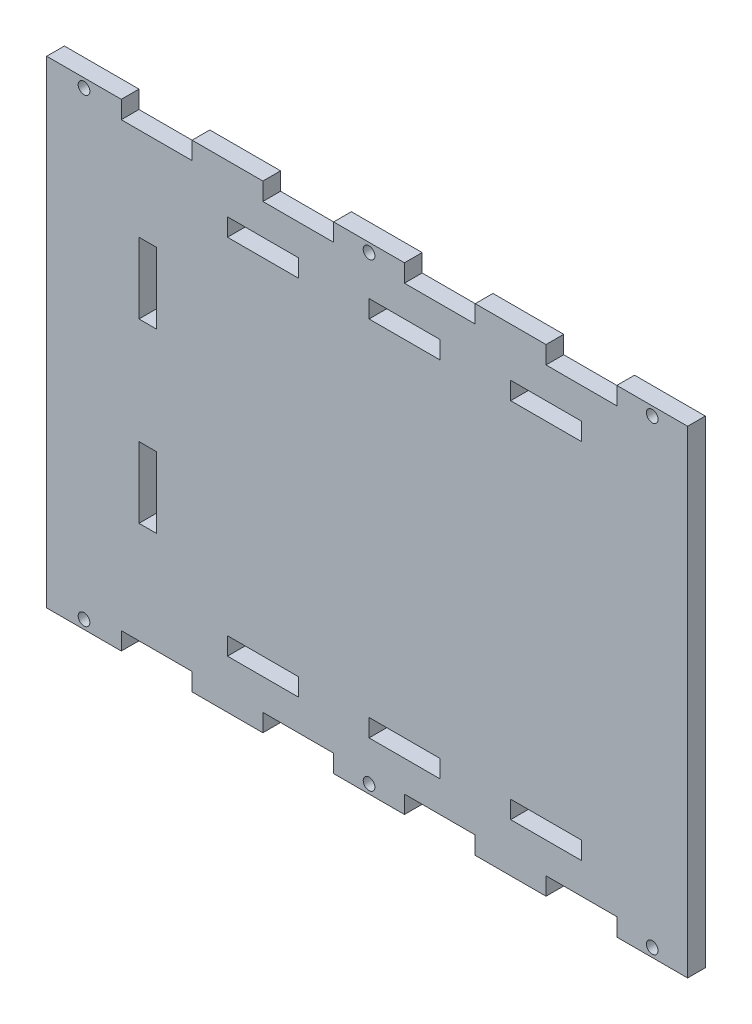
SolidWorks part; units mm, degrees
ref_plane "Front Plane" through (0, 0, 0) normal (0, 0, 1) x (1, 0, 0)
ref_plane "Top Plane" through (0, 0, 0) normal (0, 1, 0) x (1, 0, 0)
ref_plane "Right Plane" through (0, 0, 0) normal (1, 0, 0) x (0, 0, -1)
sketch "Sketch1" plane through (0, 0, 0) normal (0, 0, 1) x (1, 0, 0)
  line L1 (90.6195, 155.575) -> (-139.3499, 155.575)
  line L2 (90.6195, 155.575) -> (90.6195, -15.875)
  line L3 (90.6195, -15.875) -> (-139.3499, -15.875)
  line L4 (-139.3499, 155.575) -> (-139.3499, -15.875)
extrude "Boss-Extrude1" add sketch "Sketch1" along normal blind 6.35
sketch "Sketch2" plane through (0, 0, 6.35) normal (0, 0, 1) x (1, 0, 0)
  line L0 (-139.3499, -15.875) -> (90.6195, -15.875) construction
  line L1 (-112.5805, -9.525) -> (-87.1805, -9.525)
  line L2 (-112.5805, -9.525) -> (-112.5805, -15.875)
  line L3 (-112.5805, -15.875) -> (-87.1805, -15.875)
  line L4 (-87.1805, -9.525) -> (-87.1805, -15.875)
  line L5 (-87.1805, -9.525) -> (-87.1805, -15.875) construction
  line L6 (90.6195, 155.575) -> (-139.3499, 155.575) construction
  line L7 (-112.5805, 149.225) -> (-87.1805, 149.225)
  line L8 (-112.5805, 149.225) -> (-112.5805, 155.575)
  line L9 (-112.5805, 155.575) -> (-87.1805, 155.575)
  line L10 (-87.1805, 149.225) -> (-87.1805, 155.575)
  line L11 (-87.1805, 149.225) -> (-87.1805, 155.575) construction
extrude "Cut-Extrude1" cut sketch "Sketch2" against normal blind 6.35
pattern_linear "LPattern1" count 4 spacing 50.8 along (1, 0, 0) of "Cut-Extrude1"
sketch "Sketch4" plane through (0, 0, 0) normal (0, 0, -1) x (-1, 0, 0)
  line L0 (128.0988, -9.525) -> (123.8316, -15.875) construction
  line L1 (139.3499, -15.875) -> (112.5805, -15.875) construction
  line L2 (123.8316, -9.525) -> (123.8316, -15.875) construction
  line L3 (123.8316, -9.525) -> (128.0988, -15.875) construction
  line L4 (128.0988, -9.525) -> (128.0988, -15.875) construction
  line L5 (21.5469, -9.525) -> (25.8141, -15.875) construction
  line L6 (36.3805, -15.875) -> (10.9805, -15.875) construction
  line L7 (25.8141, -9.525) -> (25.8141, -15.875) construction
  line L8 (25.8141, -9.525) -> (21.5469, -15.875) construction
  line L9 (-75.7859, -9.525) -> (-80.0531, -15.875) construction
  line L10 (-65.2195, -15.875) -> (-90.6195, -15.875) construction
  line L11 (-80.0531, -9.525) -> (-80.0531, -15.875) construction
  line L12 (-80.0531, -9.525) -> (-75.7859, -15.875) construction
  line L13 (123.8316, 149.225) -> (128.0988, 155.575) construction
  line L14 (112.5805, 155.575) -> (139.3499, 155.575) construction
  line L15 (128.0988, 149.225) -> (128.0988, 155.575) construction
  line L16 (128.0988, 149.225) -> (123.8316, 155.575) construction
  line L17 (21.5469, 149.225) -> (25.8141, 155.575) construction
  line L18 (10.9805, 155.575) -> (36.3805, 155.575) construction
  line L19 (25.8141, 149.225) -> (25.8141, 155.575) construction
  line L20 (25.8141, 149.225) -> (21.5469, 155.575) construction
  line L21 (-75.7859, 149.225) -> (-80.0531, 155.575) construction
  line L22 (-90.6195, 155.575) -> (-65.2195, 155.575) construction
  line L23 (-80.0531, 149.225) -> (-75.7859, 155.575) construction
  line L24 (-75.7859, 149.225) -> (-75.7859, 155.575) construction
  circle A0 centre (-77.9195, -12.7) radius 2.0955
  circle A1 centre (23.6805, -12.7) radius 2.0955
  circle A2 centre (125.9652, -12.7) radius 2.0955
  circle A3 centre (125.9652, 152.4) radius 2.0955
  circle A4 centre (23.6805, 152.4) radius 2.0955
  circle A5 centre (-77.9195, 152.4) radius 2.0955
  dimension "D1" = 4.191
extrude "Cut-Extrude2" cut sketch "Sketch4" against normal through all
sketch "Sketch5" plane through (0, 0, 0) normal (0, 0, -1) x (-1, 0, 0)
  line L0 (-1.7195, 7.9375) -> (23.6805, 7.9375) construction
  line L1 (-52.5195, 1.5875) -> (-27.1195, 1.5875)
  line L2 (-52.5195, 1.5875) -> (-52.5195, 7.9375)
  line L3 (-52.5195, 7.9375) -> (-27.1195, 7.9375)
  line L4 (-27.1195, 1.5875) -> (-27.1195, 7.9375)
  line L5 (-1.7195, 1.5875) -> (23.6805, 1.5875)
  line L6 (-1.7195, 1.5875) -> (-1.7195, 7.9375)
  line L7 (-1.7195, 7.9375) -> (23.6805, 7.9375)
  line L8 (23.6805, 1.5875) -> (23.6805, 7.9375)
  line L9 (106.2305, 90.4875) -> (106.2305, 115.8875) construction
  line L10 (49.0805, 1.5875) -> (74.4805, 1.5875)
  line L11 (49.0805, 1.5875) -> (49.0805, 7.9375)
  line L12 (49.0805, 7.9375) -> (74.4805, 7.9375)
  line L13 (74.4805, 1.5875) -> (74.4805, 7.9375)
  line L14 (99.8805, 26.9875) -> (106.2305, 26.9875)
  line L15 (99.8805, 26.9875) -> (99.8805, 52.3875)
  line L16 (99.8805, 52.3875) -> (106.2305, 52.3875)
  line L17 (106.2305, 26.9875) -> (106.2305, 52.3875)
  line L18 (99.8805, 90.4875) -> (106.2305, 90.4875)
  line L19 (99.8805, 90.4875) -> (99.8805, 115.8875)
  line L20 (99.8805, 115.8875) -> (106.2305, 115.8875)
  line L21 (106.2305, 90.4875) -> (106.2305, 115.8875)
  line L22 (106.2305, 115.8875) -> (99.8805, 115.8875) construction
  line L24 (49.0805, 131.7625) -> (74.4805, 131.7625)
  line L25 (49.0805, 131.7625) -> (49.0805, 138.1125)
  line L26 (49.0805, 138.1125) -> (74.4805, 138.1125)
  line L27 (74.4805, 131.7625) -> (74.4805, 138.1125)
  line L28 (-1.7195, 131.7625) -> (23.6805, 131.7625)
  line L29 (-1.7195, 131.7625) -> (-1.7195, 138.1125)
  line L30 (-1.7195, 138.1125) -> (23.6805, 138.1125)
  line L31 (23.6805, 131.7625) -> (23.6805, 138.1125)
  line L32 (-27.1195, 138.1125) -> (-52.5195, 138.1125)
  line L33 (-27.1195, 138.1125) -> (-27.1195, 131.7625)
  line L34 (-27.1195, 131.7625) -> (-52.5195, 131.7625)
  line L35 (-52.5195, 138.1125) -> (-52.5195, 131.7625)
extrude "Cut-Extrude3" cut sketch "Sketch5" against normal blind 6.35
